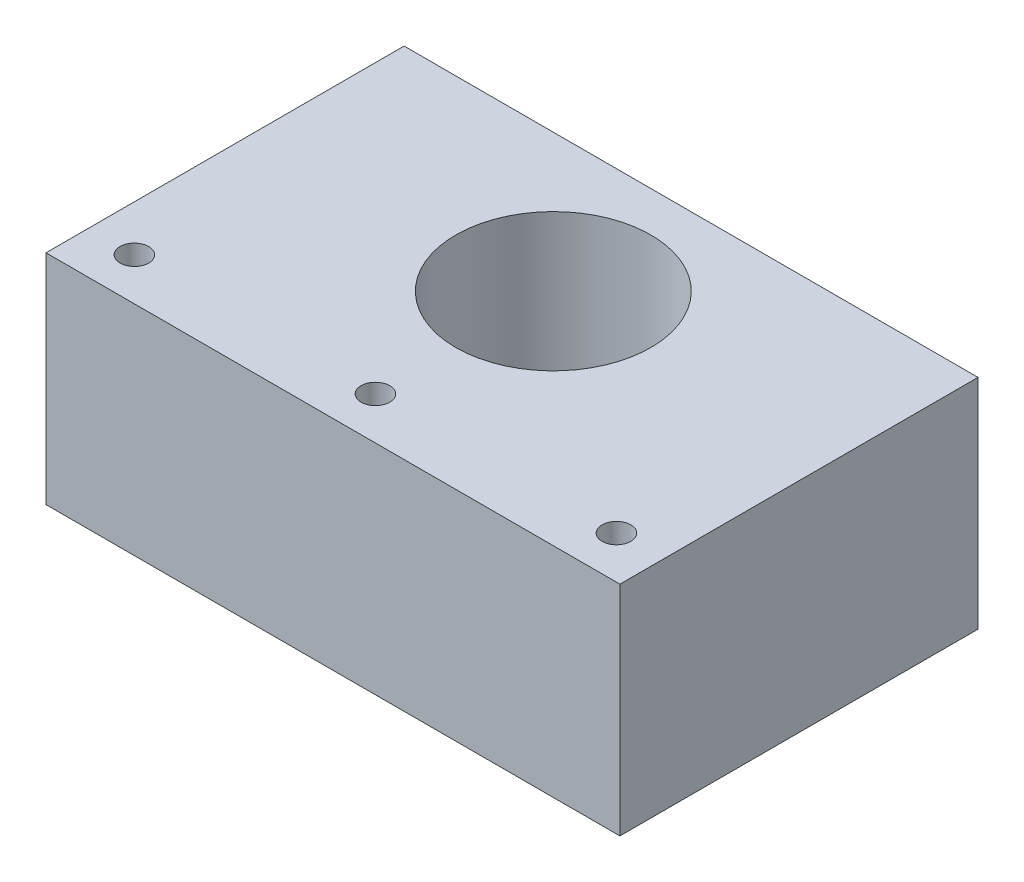
SolidWorks part; units mm, degrees
ref_plane "Front Plane" through (0, 0, 0) normal (0, 0, 1) x (1, 0, 0)
ref_plane "Top Plane" through (0, 0, 0) normal (0, 1, 0) x (1, 0, 0)
ref_plane "Right Plane" through (0, 0, 0) normal (1, 0, 0) x (0, 0, -1)
sketch "Sketch1" plane through (0, 0, 0) normal (0, 0, 1) x (1, 0, 0)
  line L1 (-31.75, 12.7) -> (31.75, 12.7)
  line L2 (-31.75, 12.7) -> (-31.75, -12.7)
  line L3 (-31.75, -12.7) -> (31.75, -12.7)
  line L4 (31.75, 12.7) -> (31.75, -12.7)
  point P4 (-31.75, 0)
  point P6 (0, 12.7)
  dimension "D1" = 63.5
  dimension "D2" = 25.4
extrude "Boss-Extrude1" add sketch "Sketch1" along normal blind 38.1
sketch "Sketch2" plane through (0, -12.7, 0) normal (0, -1, 0) x (1, 0, 0)
  line L0 (0, 0) -> (0, 102.7115) construction
  line L1 (-31.75, 0) -> (31.75, 0) construction
  circle A0 centre (24.765, 15.24) radius 3.175
  circle A1 centre (0, 15.24) radius 8.763
  circle A2 centre (-24.765, 15.24) radius 3.175
  dimension "D1" = 17.526
  dimension "D2" = 6.35
  dimension "D3" = 6.35
  dimension "D4" = 15.24
  dimension "D5" = 15.24
  dimension "D6" = 49.53
extrude "Cut-Extrude1" cut sketch "Sketch2" against normal blind 12.7 contours A2 | A0 region at (-24.765, -12.7, 15.24)
extrude "Cut-Extrude2" cut sketch "Sketch2<3>" against normal blind 4.826 contours A1
sketch "Sketch2<3>" plane through (0, -12.7, 0) normal (0, -1, 0) x (1, 0, 0) same geometry as "Sketch2"
sketch "Sketch3" plane through (0, -7.874, 0) normal (0, -1, 0) x (1, 0, 0)
  circle A0 centre (0, 15.24) radius 6.35
  dimension "D1" = 12.7
extrude "Cut-Extrude3" cut sketch "Sketch3" against normal up to vertex (20.574 mm away) up to point (31.75, 12.7, 0)
sketch "Sketch4" plane through (0, 12.7, 0) normal (0, 1, 0) x (1, 0, 0)
  line L0 (31.75, 0) -> (-31.75, 0) construction
  circle A0 centre (0, -15.24) radius 10.795
  point P6 (0, 0)
  dimension "D1" = 21.59
extrude "Cut-Extrude4" cut sketch "Sketch4" against normal blind 19.05
sketch "Sketch5" plane through (0, 12.7, 0) normal (0, 1, 0) x (1, 0, 0)
  line L0 (31.75, -38.1) -> (-31.75, -38.1) construction
  circle A0 centre (-26.67, -34.925) radius 1.5875
  circle A1 centre (0, -34.925) radius 1.5875
  circle A2 centre (26.67, -34.925) radius 1.5875
  dimension "D1" = 3.175
  dimension "D2" = 53.34
  dimension "D3" = 26.67
  dimension "D4" = 3.175
extrude "Cut-Extrude5" cut sketch "Sketch5" against normal blind 50.8
sketch "Sketch6" plane through (0, 0, 38.1) normal (0, 0, 1) x (1, 0, 0)
  line L0 (31.75, -12.7) -> (31.75, 12.7) construction
  line L1 (-31.75, -12.7) -> (31.75, -12.7)
  line L2 (-31.75, -12.7) -> (-31.75, -11.43)
  line L3 (-31.75, -11.43) -> (31.75, -11.43)
  line L4 (31.75, -12.7) -> (31.75, -11.43)
  dimension "D1" = 1.27
extrude "Cut-Extrude6" cut sketch "Sketch6" against normal up to vertex (38.1 mm away) up to point (-31.75, -12.7, 0)
sketch "Sketch7" plane through (0, 0, 38.1) normal (0, 0, 1) x (1, 0, 0)
  line L4 (-31.75, -11.43) -> (31.75, -11.43)
  line L5 (31.75, -11.43) -> (31.75, 12.7)
  line L6 (31.75, 12.7) -> (-31.75, 12.7)
  line L7 (-31.75, 12.7) -> (-31.75, -11.43)
  line L8 (-31.75, -11.43) -> (31.75, -11.43)
  line L9 (31.75, -11.43) -> (31.75, 12.7)
  line L10 (31.75, 12.7) -> (-31.75, 12.7)
  line L11 (-31.75, 12.7) -> (-31.75, -11.43)
  dimension "D1" = 0
extrude "Boss-Extrude2" add sketch "Sketch7" along normal blind 1.524
sketch "Sketch8" plane through (0, -11.43, 0) normal (0, -1, 0) x (1, 0, 0)
  line L0 (0, 48.3428) -> (0, -10.6506) construction
  line L1 (6.35, 15.24) -> (-20.3951, 15.24) construction
  circle A0 centre (0, 15.24) radius 6.35 construction
  circle A1 centre (12.3302, 2.91) radius 1.7
  circle A2 centre (12.3302, 27.57) radius 1.7
  circle A3 centre (-12.3302, 27.57) radius 1.7
  circle A4 centre (-12.3302, 2.91) radius 1.7
  circle A5 centre (12.3302, 27.57) radius 2.462
  circle A6 centre (12.3302, 2.91) radius 2.462
  circle A7 centre (-12.3302, 2.91) radius 2.462
  circle A8 centre (-12.3302, 27.57) radius 2.462
  dimension "D1" = 12.33
  dimension "D2" = 3.4
  dimension "D3" = 12.3302
  dimension "D4" = 0.762
